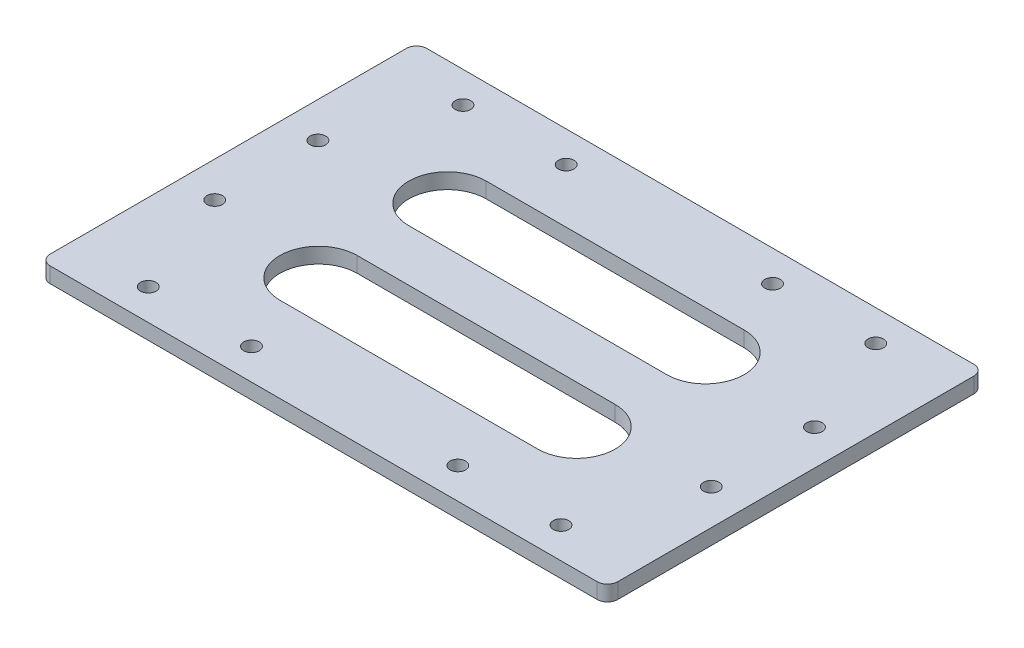
SolidWorks part; units mm, degrees
ref_plane "前视基准面" through (0, 0, 0) normal (0, 0, 1) x (1, 0, 0)
ref_plane "上视基准面" through (0, 0, 0) normal (0, 1, 0) x (1, 0, 0)
ref_plane "右视基准面" through (0, 0, 0) normal (1, 0, 0) x (0, 0, -1)
other "Configuration Table"
sketch "草图1" plane through (0, 0, 0) normal (0, 1, 0) x (1, 0, 0)
  line L0 (-40, 30.5) -> (-20, 30.5) construction
  line L1 (-55, 36.5) -> (55, 36.5)
  line L2 (-55, 36.5) -> (-55, -36.5)
  line L3 (-55, -36.5) -> (55, -36.5)
  line L4 (55, 36.5) -> (55, -36.5)
  line L5 (-55, 36.5) -> (55, -36.5) construction
  line L6 (-55, -36.5) -> (55, 36.5) construction
  line L7 (0, 0) -> (0, 36.5) construction
  line L8 (-48.125, 10.5) -> (-48.125, -9.5) construction
  line L9 (48.125, 10.5) -> (48.125, -9.5) construction
  line L10 (40, 30.5) -> (20, 30.5) construction
  line L11 (0, 0) -> (55, 0) construction
  line L12 (40, -30.5) -> (20, -30.5) construction
  line L13 (-40, -30.5) -> (-20, -30.5) construction
  circle A0 centre (-40, 30.5) radius 1.5
  circle A1 centre (-20, 30.5) radius 1.5
  circle A2 centre (-48.125, 10.5) radius 1.5
  circle A3 centre (-48.125, -9.5) radius 1.5
  circle A4 centre (48.125, -9.5) radius 1.5
  circle A5 centre (48.125, 10.5) radius 1.5
  circle A6 centre (20, 30.5) radius 1.5
  circle A7 centre (40, 30.5) radius 1.5
  circle A8 centre (40, -30.5) radius 1.5
  circle A9 centre (20, -30.5) radius 1.5
  circle A10 centre (-20, -30.5) radius 1.5
  circle A11 centre (-40, -30.5) radius 1.5
  point P0 (0, 0)
  dimension "D5" = 3
  dimension "D1" = 110
  dimension "D2" = 73
  dimension "D3" = 20
  dimension "D4" = 20
  dimension "D6" = 96.25
  dimension "D7" = 6
  dimension "D8" = 40
  dimension "D9" = 26
extrude "凸台-拉伸1" add sketch "草图1" along normal blind 3
sketch "草图2" plane through (0, 3, 0) normal (0, 1, 0) x (1, 0, 0)
  line L0 (-25, 12.5) -> (25, 12.5) construction
  line L1 (-25, 20) -> (25, 20)
  line L2 (-25, 5) -> (25, 5)
  line L3 (0, 0) -> (55, 0) construction
  line L4 (55, -36.5) -> (55, 36.5) construction
  line L5 (0, 0) -> (0, 12.5) construction
  line L6 (-25, -12.5) -> (25, -12.5) construction
  line L7 (-25, -20) -> (25, -20)
  line L8 (-25, -5) -> (25, -5)
  arc A0 (-25, 20) -> (-25, 5) centre (-25, 12.5) ccw
  arc A1 (25, 5) -> (25, 20) centre (25, 12.5) ccw
  arc A2 (-25, -20) -> (-25, -5) centre (-25, -12.5) cw
  arc A3 (25, -5) -> (25, -20) centre (25, -12.5) cw
  point P2 (0, 12.5)
  point P16 (0, -12.5)
  dimension "D1" = 7.5
  dimension "D2" = 10
  dimension "D3" = 50
extrude "切除-拉伸1" cut sketch "草图2" against normal blind 10
fillet "圆角1" radius 2 4 edges at (55, 1.5, 36.5) (-55, 1.5, -36.5) (55, 1.5, -36.5) (-55, 1.5, 36.5)
